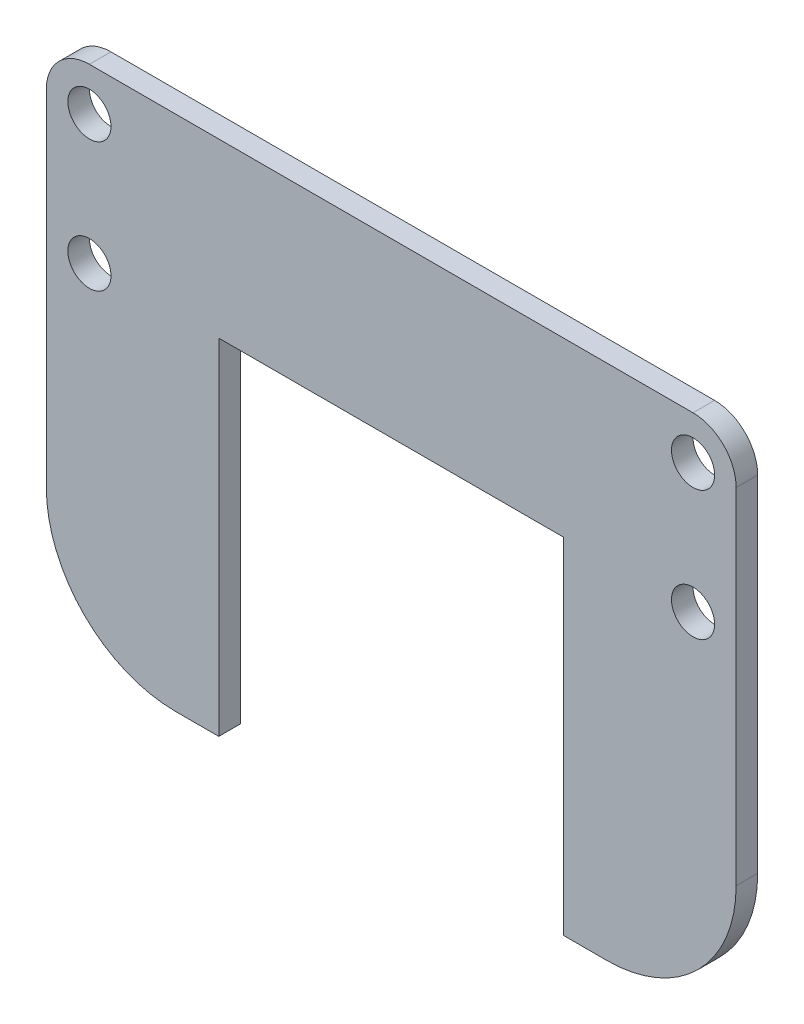
SolidWorks part; units mm, degrees
ref_plane "Front Plane" through (0, 0, 0) normal (0, 0, 1) x (1, 0, 0)
ref_plane "Top Plane" through (0, 0, 0) normal (0, 1, 0) x (1, 0, 0)
ref_plane "Right Plane" through (0, 0, 0) normal (1, 0, 0) x (0, 0, -1)
sketch "Sketch1" plane through (0, 0, 0) normal (0, 0, 1) x (1, 0, 0)
  line L4 (12.7, -12.7) -> (12.7, 12.7)
  line L5 (12.7, -12.7) -> (-12.7, -12.7)
  line L6 (0, -12.7) -> (0, 12.7) construction
  line L9 (25.4, 25.4) -> (25.4, -12.7)
  line L10 (25.4, -12.7) -> (12.7, -12.7)
  line L11 (12.7, 12.7) -> (-12.7, 12.7)
  line L12 (12.7, 12.7) -> (25.4, 12.7) construction
  line L13 (0, 12.7) -> (0, 25.4) construction
  line L14 (-25.4, 25.4) -> (25.4, 25.4)
  line L15 (22.225, 22.225) -> (19.05, 22.225) construction
  line L16 (22.225, 19.05) -> (22.225, 22.225) construction
  line L17 (22.225, 22.225) -> (41.275, 22.225) construction
  line L18 (22.225, 22.225) -> (22.225, 41.275) construction
  line L19 (-22.225, 22.225) -> (-22.225, 41.275) construction
  line L20 (-22.225, 22.225) -> (-41.275, 22.225) construction
  line L21 (-22.225, 19.05) -> (-22.225, 22.225) construction
  line L22 (-22.225, 22.225) -> (-19.05, 22.225) construction
  line L23 (-12.7, 12.7) -> (-25.4, 12.7) construction
  line L24 (-25.4, -12.7) -> (-12.7, -12.7)
  line L25 (-25.4, 25.4) -> (-25.4, -12.7)
  line L26 (-12.7, -12.7) -> (-12.7, 12.7)
  circle A0 centre (22.225, 12.7) radius 1.5875
  circle A1 centre (22.225, 12.7) radius 6.35 construction
  circle A2 centre (22.225, 22.225) radius 1.5875
  circle A3 centre (-22.225, 12.7) radius 6.35 construction
  circle A4 centre (-22.225, 22.225) radius 1.5875
  circle A5 centre (-22.225, 12.7) radius 1.5875
  point P0 (0, 0)
  point P2 (0, 0)
  point P18 (22.225, 19.05)
  point P21 (22.225, 21.7425)
  point P22 (25.4, 26.1797)
  point P23 (39.4348, 22.225)
  dimension "D2" = 3.175
  dimension "D5" = 12.7
  dimension "D7" = 3.175
  dimension "D1" = 12.7
  dimension "D3" = 3.175
  dimension "D4" = 25.4
  dimension "D6" = 12.7
  dimension "D8" = 3.175
  dimension "D9" = 19.05
extrude "Boss-Extrude1" add sketch "Sketch1" along normal blind 1.5875 contours L14 L13 L11 L4 L10 L9 A2 A0 region at (13.335, 0, 0)
fillet "Fillet1" radius 9.525 2 edges at (25.4, -12.7, 0.7937) (-25.4, -12.7, 0.7937)
fillet "Fillet2" radius 3.175 2 edges at (25.4, 25.4, 0.7937) (-25.4, 25.4, 0.7937)
